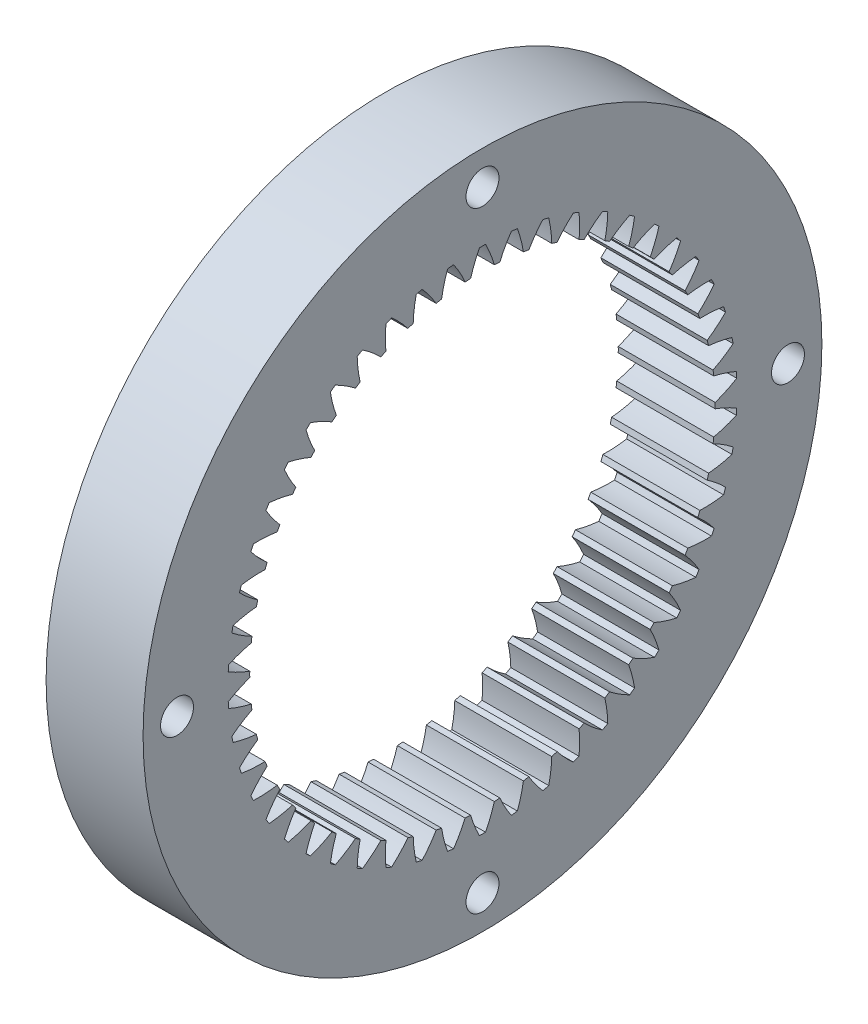
SolidWorks part; units mm, degrees
ref_plane "Plane1" through (0, 0, 0) normal (0, 0, 1) x (1, 0, 0)
ref_plane "Plane2" through (0, 0, 0) normal (0, 1, 0) x (1, 0, 0)
ref_plane "Plane3" through (0, 0, 0) normal (1, 0, 0) x (0, 0, -1)
sketch "HoldingSke" plane through (0, 0, 0) normal (0, 1, 0) x (1, 0, 0)
  line L0 (0, 0) -> (0.6428, -0.766)
  line L1 (-15, 0) -> (100, 0) construction
  line L2 (0, 0) -> (-2.1039, 2.3779)
  line L3 (0, 0) -> (-11.863, 4.5341)
  line L4 (0, 0) -> (5.5511, 6.6156)
  line L5 (0, 0) -> (-23.7986, -8.8762)
  line L6 (0, 0) -> (-10.5278, -7.1032)
  line L7 (-2.1039, 2.3779) -> (3.3635, 27.1825)
  line L8 (-76.2, 3.3779) -> (-54.61, 3.3779)
  line L9 (-71.009, 38.7566) -> (-53.1078, 45.2721)
  line L10 (-76.2, 71.12) -> (104.1128, 71.12)
  line L11 (0, 0) -> (-10, 0)
  line L12 (-76.2, 101.6) -> (-76.162, 101.6)
  line L13 (24.9733, 27.94) -> (52.9518, 28.4284)
  line L14 (24.9733, 27.94) -> (24.9743, 27.94)
  line L15 (24.9733, 27.94) -> (100.4006, 29.5858)
  circle A0 centre (0, 0) radius 35
  circle A1 centre (0, 0) radius 12.7
  circle A2 centre (0, 0) radius 12.7
  dimension "Num_teeth" = 50
  dimension "Pitch_radius" = 180.3128
  dimension "Width" = 10
  dimension "Diameter" = 70
sketch "BasProSke" plane through (0, 0, 0) normal (0, 1, 0) x (1, 0, 0)
  line L0 (-10, 0) -> (60, 0) construction
  line L1 (0, 24) -> (0, 35)
  line L2 (0, 24) -> (10, 24)
  line L3 (10, 24) -> (10, 35)
  line L4 (10, 35) -> (0, 35)
  dimension "Thickness" = 10
  dimension "Diameter" = 70
revolve "Base-Revolve" add sketch "BasProSke" angle 360 about L0
sketch "TooCutSke" plane through (0, 0, 0) normal (1, 0, 0) x (0, 0, -1)
  line L3 (0.8803, 24.9845) -> (0.8803, 53.6633) construction
  line L4 (0, 0) -> (0, 59.563) construction
  line L5 (0, 0) -> (-4.2903, 68.1927) construction
  line L6 (-10.7899, 20.506) -> (36.4405, 23.4775) construction
  circle A0 centre (0, 0) radius 25 construction
  circle A1 centre (0, 0) radius 26.251 construction
  circle A2 centre (0, 0) radius 21.1431 construction
  circle A3 centre (0, 0) radius 23.9746 construction
  arc A4 (1.2282, 23.9431) -> (0.3126, 26.2491) centre (-10.7899, 20.506) ccw
  arc A5 (1.2282, 23.9431) -> (-1.2282, 23.9431) centre (0, 0) ccw
  arc A6 (0.3126, 26.2491) -> (-0.3126, 26.2491) centre (0, 0) ccw
  arc A7 (-0.3126, 26.2491) -> (-1.2282, 23.9431) centre (10.7899, 20.506) ccw
extrude "ToothCut" cut sketch "TooCutSke" along normal through all
fillet "Breaks" [suppressed] radius 0.1
fillet "RootFillets" [suppressed] radius 0.251
pattern_circular "TeethCuts" count 50 every 7.2 about axis through (-10, 0, 0) along (1, 0, 0) of "RootFillets", "Breaks", "ToothCut"
sketch "Croquis2" plane through (0, 0, 0) normal (-1, 0, 0) x (0, 0, 1)
  circle A0 centre (0, 0) radius 25 construction
  circle A1 centre (31.5, 0) radius 1.7
  circle A2 centre (0, 0) radius 31.5 construction
  circle A3 centre (0, 31.5) radius 1.7
  circle A6 centre (0, -31.5) radius 1.7
  circle A7 centre (-31.5, 0) radius 1.7
  point P13 (0, 0)
  point P16 (0, 0)
  dimension "D1" = 50
  dimension "D2" = 63
  dimension "D3" = 3.4
  dimension "D4" = 4
extrude "Cortar-Extruir1" cut sketch "Croquis2" against normal up to surface (10 mm away) up to face at (10, 0, 35)
equation "' \"Module@HoldingSke\" = 6.35"
equation "' \"Num_teeth@HoldingSke\" = 24"
equation "' \"Ap@HoldingSke\" =  14.5"
equation "' \"Ap@HoldingSke\" = 14.5"
equation "' \"Width@HoldingSke\" = 12"
equation "' \"Diameter@HoldingSke\" = 8 * 25.4"
equation "' \"Show_teeth@HoldingSke\" = 100"
equation "' \"Backlash@HoldingSke\" = 0.009 * 25.4"
equation "' \"Addendum_fac@HoldingSke\" = 1.0"
equation "' \"Dedendum_fac@HoldingSke\" = 1.25"
equation "' \"Dedendum_add@HoldingSke\" = 0.00005 * 25.4"
equation "' \"Clearance_fac@HoldingSke\" = 0.25"
equation "\"Pitch@HoldingSke\" = 1 / \"Module@HoldingSke\" "
equation "\"Overcut_dia@TooCutSke\" = (\"Num_teeth@HoldingSke\" - 2 * \"Addendum_fac@HoldingSke\") / \"Pitch@HoldingSke\" - 0.002 * 25.4"
equation "\"Pitch_dia@TooCutSke\" = \"Num_teeth@HoldingSke\" / \"Pitch@HoldingSke\""
equation "\"Base_dia@TooCutSke\" = \"Num_teeth@HoldingSke\" / \"Pitch@HoldingSke\" * cos((\"Ap@HoldingSke\"  * 3.14159265 / 180)) * 0.90"
equation "\"Root_dia@TooCutSke\" = \"Num_teeth@HoldingSke\"  / \"Pitch@HoldingSke\" + 2 *  \"Dedendum_fac@HoldingSke\"/ \"Pitch@HoldingSke\" + \"Dedendum_add@HoldingSke\" * 2"
equation "\"Half_ang@TooCutSke\" = 180 / \"Num_teeth@HoldingSke\""
equation "\"Half_CT@TooCutSke\" = \"Num_teeth@HoldingSke\" / \"Pitch@HoldingSke\" * sin((3.14159265 / 2 / \"Num_teeth@HoldingSke\")) / 2 + 10 * \"Backlash@HoldingSke\" / 4"
equation "\"Flank_rad@TooCutSke\" = \"Num_teeth@HoldingSke\" / \"Pitch@HoldingSke\" / 4"
equation "\"Radius@RootFillets\"= \"Clearance_fac@HoldingSke\" / \"Pitch@HoldingSke\" + \"Dedendum_add@HoldingSke\""
equation "\"Break_rad@Breaks\" = 0.02 / \"Pitch@HoldingSke\" * 5"
equation "\"Num_teeth@TeethCuts\" = int( \"Show_teeth@HoldingSke\" ) + 1"
equation "\"Num_teeth@TeethCuts\" = ((sgn( \"Num_teeth@TeethCuts\" - \"Num_teeth@HoldingSke\" )-1)*( \"Num_teeth@TeethCuts\" - \"Num_teeth@HoldingSke\" ))/-2+ \"Num_teeth@HoldingSke\""
equation "\"Num_teeth@TeethCuts\" = ((sgn( \"Num_teeth@TeethCuts\" - 2.0)+1)*( \"Num_teeth@TeethCuts\" - 2.0))/2 +2.0"
equation "\"Angle@TeethCuts\" = 360.0 / \"Num_teeth@HoldingSke\""
equation "\"Diameter@BasProSke\" = \"Num_teeth@HoldingSke\"  / \"Pitch@HoldingSke\" + 2 *  \"Dedendum_fac@HoldingSke\"/ \"Pitch@HoldingSke\" + \"Dedendum_add@HoldingSke\" * 2 + 0.002 * 25.4"
equation "\"Diameter@BasProSke\" = ((sgn( \"Diameter@BasProSke\"  - \"Diameter@HoldingSke\" )+1)*( \"Diameter@BasProSke\"  - \"Diameter@HoldingSke\" ))/2 + \"Diameter@HoldingSke\""
equation "\"Inside_diameter@BasProSke\" =  (\"Num_teeth@HoldingSke\" - 2 * \"Addendum_fac@HoldingSke\") / \"Pitch@HoldingSke\" "
equation "\"Thickness@BasProSke\"  = \"Width@HoldingSke\""
